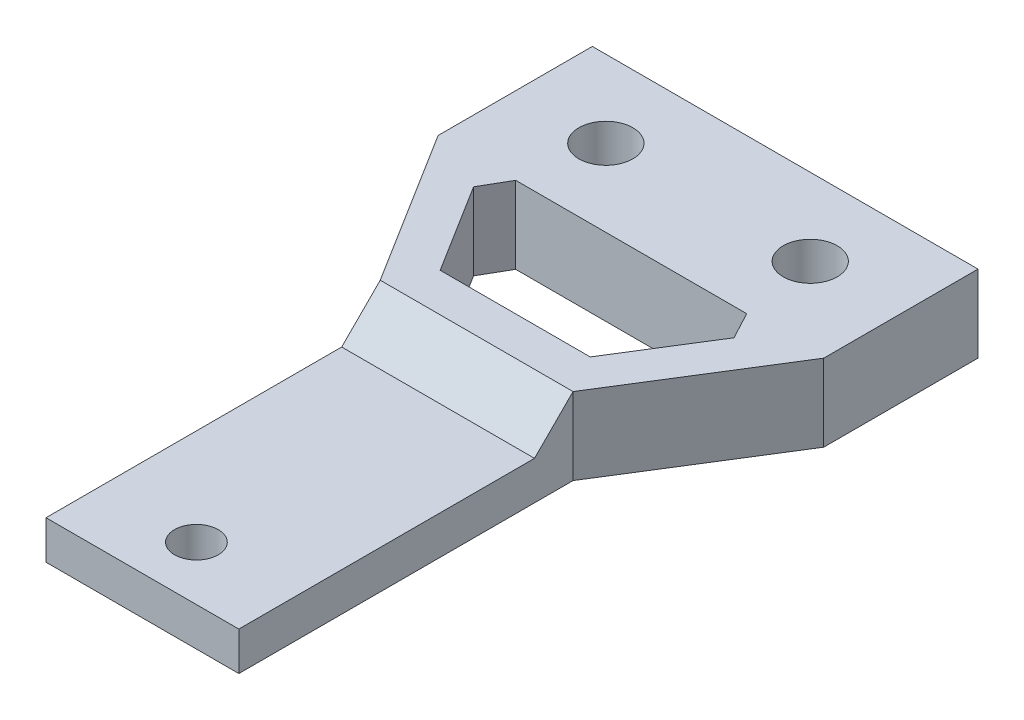
SolidWorks part; units mm, degrees
ref_plane "Front Plane" through (0, 0, 0) normal (1, 0, 0) x (0, 1, 0)
ref_plane "Top Plane" through (0, 0, 0) normal (0, 0, 1) x (0, 1, 0)
ref_plane "Right Plane" through (0, 0, 0) normal (0, 1, 0) x (-1, 0, 0)
sketch "Sketch1" plane through (0, 0, 0) normal (0, 1, 0) x (-1, 0, 0)
  line L0 (-15, -8) -> (-7.5, 4)
  line L1 (-7.5, 30) -> (7.5, 30)
  line L2 (-7.5, 30) -> (-7.5, -20)
  line L3 (-7.5, -20) -> (7.5, -20)
  line L4 (7.5, 30) -> (7.5, -20)
  line L5 (-15, -20) -> (15, -20)
  line L6 (-15, -20) -> (-15, -8)
  line L7 (-15, -8) -> (15, -8)
  line L8 (15, -20) -> (15, -8)
  line L9 (15, -8) -> (7.5, 4)
  line L10 (-7.5, 4) -> (7.5, 4)
  circle A2 centre (0, 25.8) radius 1.7
  circle A3 centre (-7.95, -14) radius 2.1
  circle A4 centre (7.95, -14) radius 2.1
  dimension "D5" = 39.8
  dimension "D6" = 7.95
  dimension "D7" = 3.4
  dimension "D19" = 4.2
  dimension "D22" = 4.2
  dimension "D8" = 7.95
  dimension "D1" = 50
  dimension "D2" = 15
  dimension "D3" = 12
  dimension "D4" = 30
  dimension "D12" = 15
  dimension "D14" = 7.5
  dimension "D15" = 30
  dimension "D16" = 7.5
  dimension "D17" = 12
  dimension "D18" = 12
  dimension "D21" = 6
  dimension "D24" = 6
extrude "Boss-Extrude1" add sketch "Sketch1" along normal blind 6 contours A3 L2 L7 L6 L5 | A4 L4 L7 L2 A3 L3 | A4 L4 L5 L8 L7 | L7 L9 L4 | L10 L2 L7 L4 | L0 L7 L2 region at (11.5369, 0, -14) region at (10, 0, -4) region at (0, 0, -2) region at (0, 0, -14) region at (-10, 0, -4) region at (-11.5369, 0, -14)
extrude "Boss-Extrude2" add sketch "Sketch1<3>" along normal blind 3 contours L2 L10 L4 L1 A2 region at (0, 0, 16.7903)
sketch "Sketch1<3>" plane through (0, 0, 0) normal (0, 1, 0) x (-1, 0, 0) same geometry as "Sketch1"
chamfer "Chamfer1" distance 3 angle 45 1 edges at (0, 3, 4)
ref_plane "Plane1" through (0, 6, 0) normal (0, 1, 0) x (-1, 0, 0)
sketch "Sketch2" plane through (0, 6, 0) normal (0, 1, 0) x (-1, 0, 0)
  line L0 (-5.8373, 1) -> (-11.4623, -8)
  line L1 (-11.4623, -8) -> (11.4623, -8)
  line L2 (11.4623, -8) -> (5.8373, 1)
  line L3 (5.8373, 1) -> (-5.8373, 1)
  line L8 (-15, -8) -> (-7.5, 4) construction
  line L9 (15, -8) -> (7.5, 4) construction
  dimension "D1" = 3
  dimension "D2" = 3
  dimension "D3" = 3
  dimension "D4" = 3
  dimension "D5" = 3
extrude "Cut-Extrude1" cut sketch "Sketch2" against normal blind 6
chamfer "Chamfer2" distance 2.5 angle 60 2 edges at (11.4623, 3, -8) (-11.4623, 3, -8) first distance on face at (8.6498, 3, -3.5) first distance on face at (0, 3, -8)
